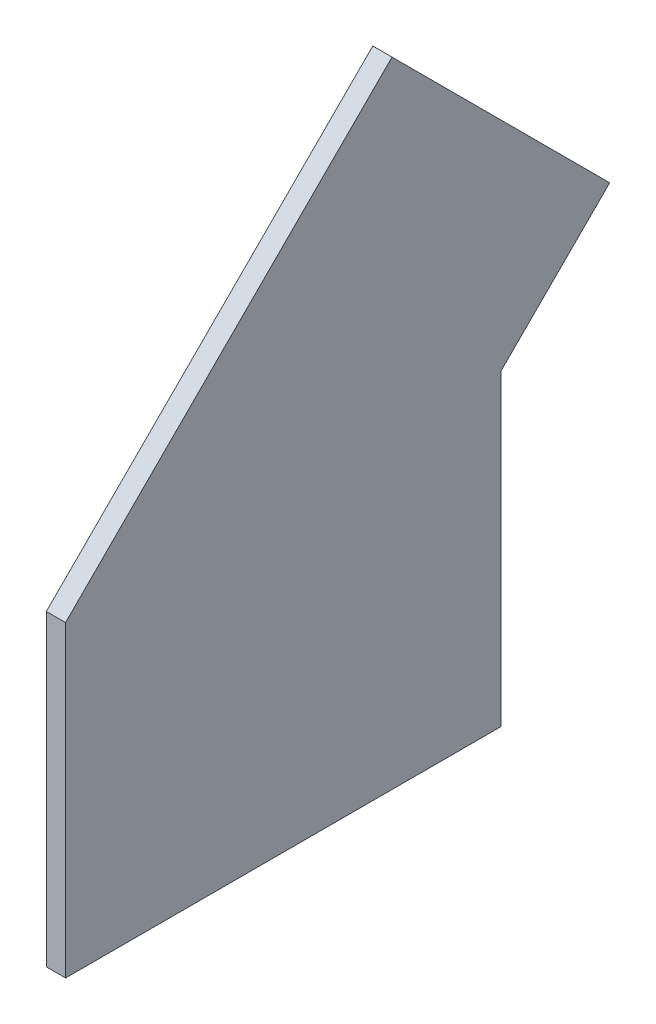
SolidWorks part; units mm, degrees
material "6061-T6 (SS)"
ref_plane "Front Plane" through (0, 0, 0) normal (0, 0, 1) x (1, 0, 0)
ref_plane "Top Plane" through (0, 0, 0) normal (0, 1, 0) x (1, 0, 0)
ref_plane "Right Plane" through (0, 0, 0) normal (1, 0, 0) x (0, 0, -1)
sketch "Sketch1" plane through (0, 0, 0) normal (1, 0, 0) x (0, 0, -1)
  line L0 (0, 0) -> (0, 50.8)
  line L2 (-17.9605, 104.6815) -> (-71.842, 50.8)
  line L3 (-71.842, 50.8) -> (-71.842, 0)
  line L4 (-71.842, 0) -> (0, 0)
  line L5 (0, 50.8) -> (17.9605, 68.7605)
  line L7 (-17.9605, 104.6815) -> (17.9605, 68.7605)
  point P4 (0, 0)
  point P7 (-73.7313, 50.8)
  dimension "D1" = 50.8
  dimension "D2" = 45
  dimension "D3" = 50.8
  dimension "D4" = 25.4
extrude "Boss-Extrude1" add sketch "Sketch1" along normal blind 3.175
